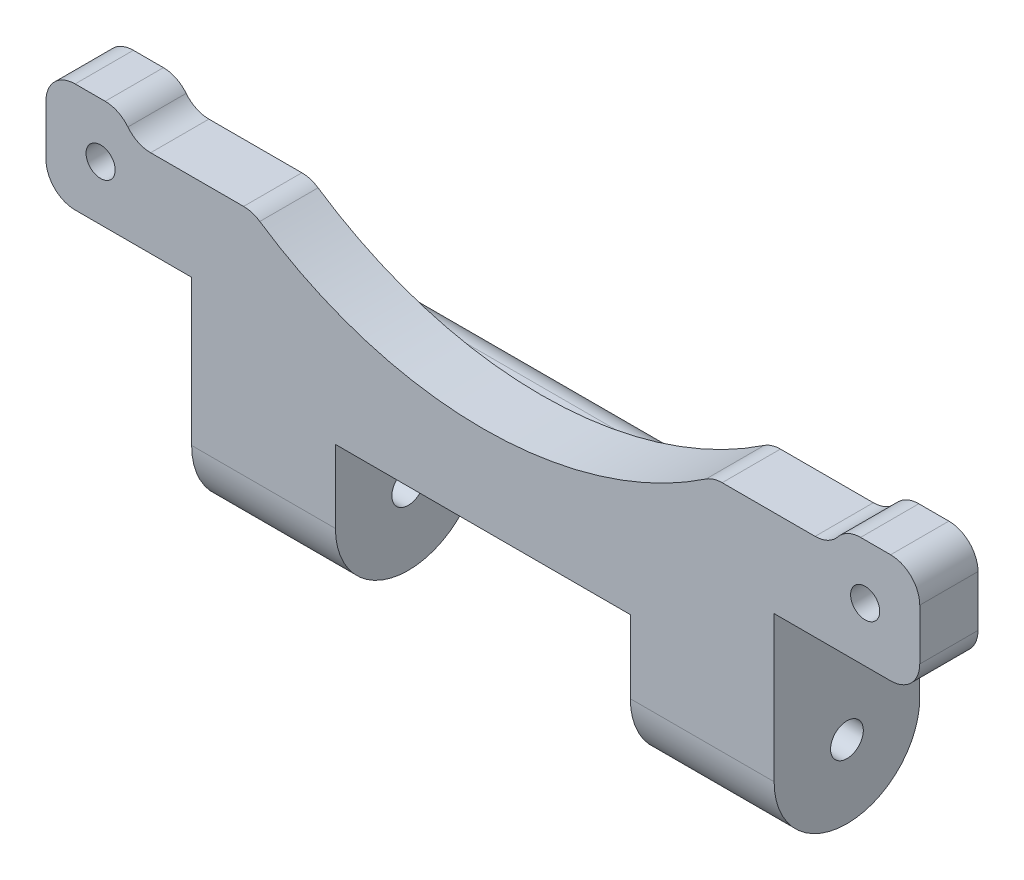
SolidWorks part; units mm, degrees
ref_plane "Front" through (0, 0, 0) normal (0, 0, 1) x (1, 0, 0)
ref_plane "Top" through (0, 0, 0) normal (0, 1, 0) x (1, 0, 0)
ref_plane "Right" through (0, 0, 0) normal (1, 0, 0) x (0, 0, -1)
sketch "Sketch1" plane through (0, 0, 0) normal (0, 1, 0) x (1, 0, 0)
  line L1 (0, 0) -> (80, 0)
  line L2 (0, 0) -> (0, -20)
  line L3 (0, -20) -> (80, -20)
  line L4 (80, 0) -> (80, -20)
  dimension "D1" = 80
  dimension "D2" = 20
extrude "Boss-Extrude1" add sketch "Sketch1" along normal blind 30
sketch "Sketch2" plane through (0, 0, 0) normal (0, -1, 0) x (-1, 0, 0)
  line L0 (0, -20) -> (-80, -20) construction
  line L1 (-19.75, -20) -> (-60.25, -20)
  line L2 (-19.75, -20) -> (-19.75, 0)
  line L3 (-19.75, 0) -> (-60.25, 0)
  line L4 (-60.25, -20) -> (-60.25, 0)
  line L5 (-80, 0) -> (0, 0) construction
  dimension "D1" = 40.5
  dimension "D2" = 19.75
extrude "Cut-Extrude1" cut sketch "Sketch2" against normal blind 20
sketch "Sketch3" plane through (0, 0, 0) normal (-1, 0, 0) x (0, 0, 1)
  line L0 (0, 0) -> (20, 0) construction
  line L1 (0, 30) -> (0, 0) construction
  circle A0 centre (10, 10) radius 2.25
  dimension "D3" = 4.5
  dimension "D1" = 10
  dimension "D2" = 10
extrude "Cut-Extrude2" cut sketch "Sketch3" against normal through all
fillet "Fillet1" radius 10 4 edges at (70.125, 0, 20) (70.125, 0, 0) (9.875, 0, 20) (9.875, 0, 0)
sketch "Sketch4" plane through (0, 30, 0) normal (0, 1, 0) x (1, 0, 0)
  line L0 (0, -20) -> (80, -20) construction
  line L1 (100, 0) -> (-20, 0)
  line L2 (100, 0) -> (100, -20)
  line L3 (100, -20) -> (-20, -20)
  line L4 (-20, 0) -> (-20, -20)
  line L5 (80, -20) -> (80, 0) construction
  dimension "D1" = 120
  dimension "D2" = 20
extrude "Boss-Extrude2" add sketch "Sketch4" along normal blind 120
sketch "Sketch7" plane through (0, 0, 0) normal (0, 0, -1) x (-1, 0, 0)
  line L0 (-100, 150) -> (-100, 30) construction
  line L1 (-88, 138) -> (8, 138)
  line L2 (-88, 138) -> (-88, 42)
  line L3 (-88, 42) -> (8, 42)
  line L4 (8, 138) -> (8, 42)
  line L5 (-100, 150) -> (20, 150) construction
  line L6 (20, 150) -> (20, 30) construction
  line L7 (0, 30) -> (20, 30) construction
  line L8 (-100, 30) -> (-80, 30) construction
  circle A0 centre (-92.5, 37.5) radius 2
  circle A1 centre (12.5, 37.5) radius 2
  circle A2 centre (12.5, 142.5) radius 2
  circle A3 centre (-92.5, 142.5) radius 2
  dimension "D5" = 4
  dimension "D1" = 12
  dimension "D2" = 12
  dimension "D3" = 12
  dimension "D4" = 12
  dimension "D6" = 7.5
  dimension "D7" = 7.5
  dimension "D8" = 2
  dimension "D9" = 2
extrude "Cut-Extrude5" cut sketch "Sketch7" against normal through all
sketch "Sketch8" plane through (0, 0, 0) normal (0, 0, -1) x (-1, 0, 0)
  line L0 (-100, 150) -> (-100, 30) construction
  line L1 (20, 150) -> (-100, 150)
  line L2 (20, 150) -> (20, 25)
  line L3 (20, 25) -> (-100, 25)
  line L4 (-100, 150) -> (-100, 25)
  dimension "D1" = 125
extrude "Cut-Extrude6" cut sketch "Sketch8" against normal blind 12
fillet "Fillet2" radius 4 1 edges at (40, 25, 12)
fillet "Fillet3" radius 4 1 edges at (40, 25, 0)
sketch "Sketch10" plane through (0, 0, 12) normal (0, 0, -1) x (-1, 0, 0)
  line L0 (20, 30) -> (20, 150) construction
  line L1 (20, 45) -> (-100, 45)
  line L2 (20, 45) -> (20, 150)
  line L3 (20, 150) -> (-100, 150)
  line L4 (-100, 45) -> (-100, 150)
  line L5 (0, 30) -> (20, 30) construction
  dimension "D1" = 15
extrude "Cut-Extrude7" cut sketch "Sketch10" against normal through all
sketch "Sketch11" plane through (0, 0, 12) normal (0, 0, -1) x (-1, 0, 0)
  line L0 (-88, 42) -> (8, 42) construction
  line L1 (20, 30) -> (20, 45) construction
  circle A0 centre (-40, 87) radius 55
  dimension "D1" = 110
  dimension "D2" = 45
  dimension "D3" = 60
extrude "Cut-Extrude8" cut sketch "Sketch11" against normal through all
fillet "Fillet6" radius 4 8 edges at (-20, 30, 16) (100, 30, 16) (100, 45, 16) (88, 45, 16) (8.3772, 42, 16) (71.6228, 42, 16) (-8, 45, 16) (-20, 45, 16)
fillet "Fillet7" radius 4 2 edges at (88, 42, 16) (-8, 42, 16)
